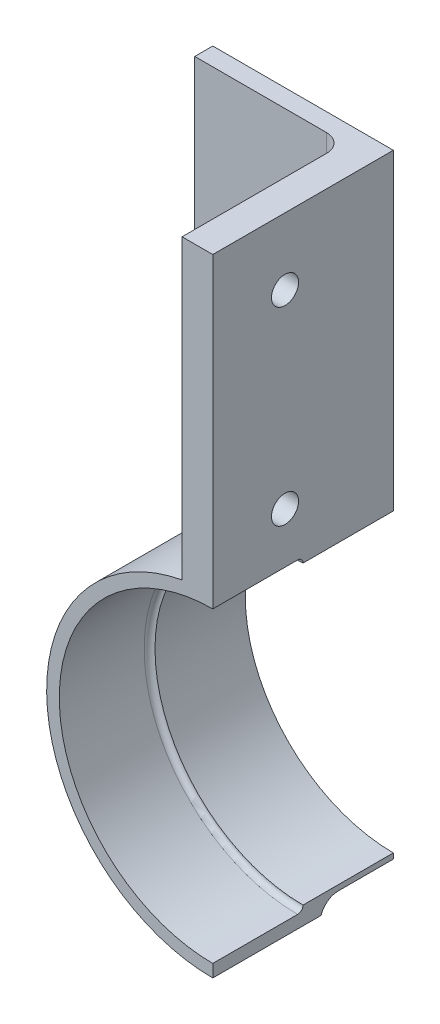
SolidWorks part; units mm, degrees
ref_plane "Front Plane" through (0, 0, 0) normal (0, 0, 1) x (1, 0, 0)
ref_plane "Top Plane" through (0, 0, 0) normal (0, 1, 0) x (1, 0, 0)
ref_plane "Right Plane" through (0, 0, 0) normal (1, 0, 0) x (0, 0, -1)
sketch "Sketch2" plane through (0, 0, 0) normal (0, 0, 1) x (1, 0, 0)
  line L0 (0, 0) -> (0, 85.598)
  line L1 (0, 85.598) -> (50.8, 85.598)
  line L2 (50.8, 85.598) -> (50.8, 0)
  line L3 (50.8, 0) -> (0, 0)
  line L5 (25.4, 85.598) -> (25.4, -2.54)
  line L7 (21.082, 85.598) -> (21.082, 41.2035)
  line L8 (29.718, 85.598) -> (29.718, 41.2035)
  circle A0 centre (25.4, 20.828) radius 21.59
  circle A1 centre (25.4, 20.828) radius 20.828
  circle A2 centre (25.4, 20.828) radius 23.368
extrude "Boss-Extrude1" add sketch "Sketch2" along normal blind 2.54 contours A2 L7 L1 L0 L3 region at (9.1348, 55.0038, 0)
extrude "Boss-Extrude3" add sketch "Sketch2<4>" along normal blind 12.7 separate body contours A1 L7 A0 L3 | A1 L5 A0 L7 | L3 A0 L5 region at (4.2933, 21.5154, 0) region at (23.2629, -0.3053, 0) region at (23.2334, 41.8887, 0)
sketch "Sketch2<4>" plane through (0, 0, 0) normal (0, 0, 1) x (1, 0, 0) same geometry as "Sketch2"
extrude "Boss-Extrude6" add sketch "Sketch2<9>" along normal blind 2.54 contours L7 A2 L3 A0 region at (2.7412, 24.0758, 0)
sketch "Sketch2<9>" plane through (0, 0, 0) normal (0, 0, 1) x (1, 0, 0) same geometry as "Sketch2"
extrude "Boss-Extrude7" add sketch "Sketch2<10>" along normal blind 25.4 contours A2 L5 L1 L7 | L5 A2 L7 A0 region at (23.2375, 64.83, 0) region at (23.2342, 43.1671, 0)
sketch "Sketch2<10>" plane through (0, 0, 0) normal (0, 0, 1) x (1, 0, 0) same geometry as "Sketch2"
extrude "Boss-Extrude8" add sketch "Sketch2<12>" along normal blind 15.24 from offset 10.16 contours L3 A2 L5 A0 | L7 A2 L3 A0 region at (2.7412, 24.0758, 0) region at (21.0415, -1.1569, 0)
sketch "Sketch2<12>" plane through (0, 0, 0) normal (0, 0, 1) x (1, 0, 0) same geometry as "Sketch2"
fillet "Fillet1" radius 2.54 2 edges at (3.8214, 21.5308, 2.54) (21.082, 63.7899, 2.54)
fillet "Fillet2" radius 2.54 1 edges at (3.9193, 18.658, 10.16)
fillet "Fillet3" radius 0.762 1 edges at (3.81, 20.828, 12.7)
sketch "Sketch3" plane through (0, 0, 0) normal (1, 0, 0) x (0, 0, -1)
  circle A0 centre (-15.24, 76.2) radius 1.905
  circle A1 centre (-15.24, 49.53) radius 1.905
extrude "Cut-Extrude1" cut sketch "Sketch3" along normal through all both and the other way through all
